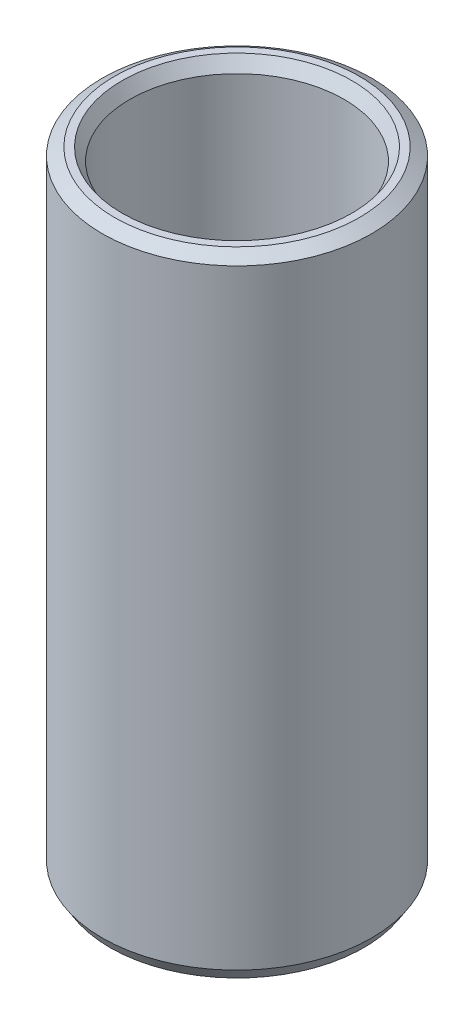
SolidWorks part; units mm, degrees
ref_plane "Front Plane" through (0, 0, 0) normal (0, 0, 1) x (1, 0, 0)
ref_plane "Top Plane" through (0, 0, 0) normal (0, 1, 0) x (1, 0, 0)
ref_plane "Right Plane" through (0, 0, 0) normal (1, 0, 0) x (0, 0, -1)
sketch "Sketch1" plane through (0, 0, 0) normal (0, 1, 0) x (1, 0, 0)
  circle A0 centre (0, 0) radius 35
  dimension "SLEEVE_OD" = 70
extrude "Boss-Extrude1" add sketch "Sketch1" along normal blind 163.6381
sketch "Sketch2" plane through (0, 0, 0) normal (0, 1, 0) x (1, 0, 0)
  circle A0 centre (0, 0) radius 27.82
  dimension "BORE_D" = 55.64
extrude "Cut-Extrude1" cut sketch "Sketch2" along normal through all
chamfer "Chamfer1" distance 2.0266 angle 57.632 4 edges at (0, 163.6381, 27.82) (0, 0, 27.82) (0, 0, 35) (0, 163.6381, 35) first distance on face at (0, 163.6381, 27.82) first distance on face at (0, 0, 27.82) first distance on face at (0, 163.6381, 35)
